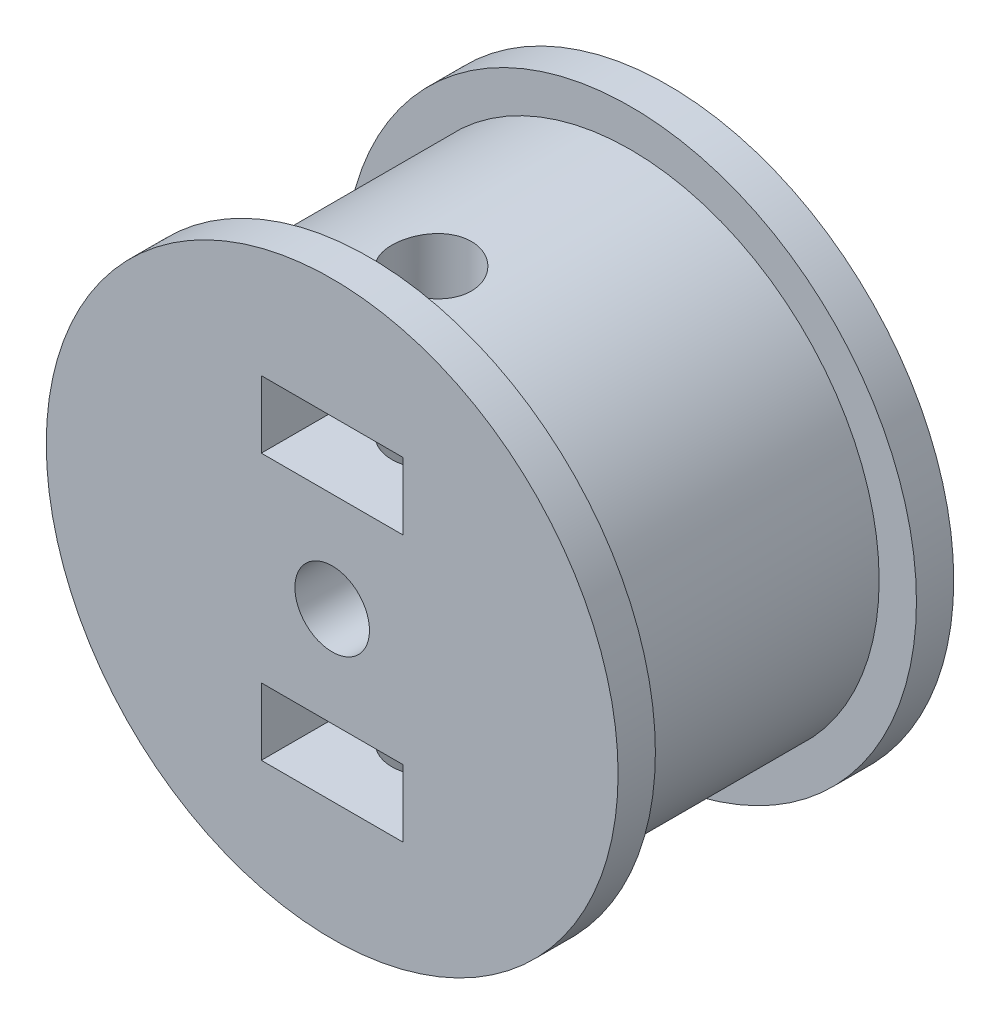
SolidWorks part; units mm, degrees
ref_plane "Спереди" through (0, 0, 0) normal (0, 0, 1) x (1, 0, 0)
ref_plane "Сверху" through (0, 0, 0) normal (0, 1, 0) x (1, 0, 0)
ref_plane "Справа" through (0, 0, 0) normal (1, 0, 0) x (0, 0, -1)
sketch "Эскиз1" plane through (0, 0, 0) normal (1, 0, 0) x (0, 0, -1)
  line L0 (0, 0) -> (30707.1807, 0) construction
  line L1 (0, 1.0651) -> (0, 30708.2458) construction
  line L2 (0, 11.5) -> (0, 1.5)
  line L3 (0, 1.5) -> (8, 1.5)
  line L4 (8, 1.5) -> (8, 7)
  line L5 (8, 7) -> (13.5, 7)
  line L6 (13.5, 7) -> (13.5, 11.5)
  line L7 (13.5, 11.5) -> (12, 11.5)
  line L8 (12, 11.5) -> (12, 10)
  line L9 (12, 10) -> (1.5, 10)
  line L10 (1.5, 10) -> (1.5, 11.5)
  line L11 (1.5, 11.5) -> (0, 11.5)
  line L12 (0, 14.5) -> (13.5, 14.5) construction
  point P7 (0, 0)
  dimension "D1" = 8
  dimension "D2" = 3
  dimension "D3" = 1.5
  dimension "D4" = 13.5
  dimension "D5" = 29
  dimension "D6" = 3
  dimension "D7" = 1.5
  dimension "D8" = 3
revolve "Повернуть1" add sketch "Эскиз1" angle 360 about L0
sketch "Эскиз2" plane through (0, 0, 0) normal (0, 1, 0) x (1, 0, 0)
  line L0 (0, 0) -> (0, 50000) construction
  line L1 (-11.5, 0) -> (11.5, 0) construction
  line L2 (-2.85, 5.6454) -> (-2.85, 2.3546)
  line L3 (-2.85, 2.3546) -> (0, 0.7091) construction
  line L4 (0, 0.7091) -> (2.85, 2.3546) construction
  line L5 (2.85, 2.3546) -> (2.85, 5.6454)
  line L6 (2.85, 5.6454) -> (0, 7.2909)
  line L7 (0, 7.2909) -> (-2.85, 5.6454)
  line L8 (-2.85, 2.3546) -> (-2.85, 0)
  line L9 (-2.85, 0) -> (2.85, 0)
  line L10 (2.85, 0) -> (2.85, 2.3546)
  circle A0 centre (0, 4) radius 1.6
  circle A1 centre (0, 4) radius 2.85 construction
  dimension "D1" = 3.2
  dimension "D2" = 4
  dimension "D3" = 5.7
extrude "Вырез-Вытянуть1" cut sketch "Эскиз2" against normal through all contours A0 region at (0, 0, -4)
extrude "Вырез-Вытянуть2" cut sketch "Эскиз2<4>" against normal blind 2.7 from offset 4 contours L9 L10 L5 L6 L7 L2 L8 A0 region at (-1.3787, 0, -6.388) offset against normal yes
sketch "Эскиз2<4>" plane through (0, 0, 0) normal (0, 1, 0) x (1, 0, 0) same geometry as "Эскиз2"
mirror "Зеркальное отражение1" about plane through (0, 0, 0) normal (0, 1, 0) of "Вырез-Вытянуть2", "Вырез-Вытянуть1"
